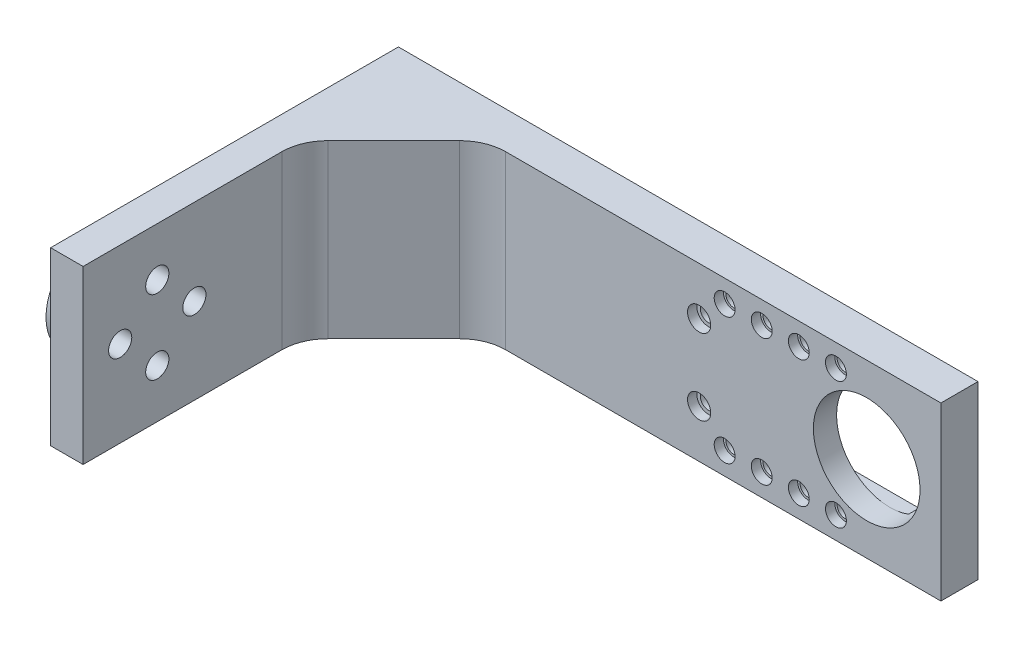
SolidWorks part; units mm, degrees
ref_plane "Front Plane" through (0, 0, 0) normal (0, 0, 1) x (1, 0, 0)
ref_plane "Top Plane" through (0, 0, 0) normal (0, 1, 0) x (1, 0, 0)
ref_plane "Right Plane" through (0, 0, 0) normal (1, 0, 0) x (0, 0, -1)
sketch "Sketch1" plane through (0, 0, 0) normal (0, 1, 0) x (1, 0, 0)
  line L0 (0, 0) -> (0, 75)
  line L1 (0, 75) -> (125, 75)
  line L2 (125, 75) -> (125, 67)
  line L3 (125, 67) -> (7, 67)
  line L4 (7, 67) -> (7, 0)
  line L5 (7, 0) -> (0, 0)
  dimension "D1" = 118
  dimension "D2" = 125
  dimension "D3" = 8
  dimension "D4" = 67
  dimension "D5" = 75
extrude "Boss-Extrude1" add sketch "Sketch1" along normal blind 37
sketch "Sketch2" plane through (0, 0, -75) normal (0, 0, -1) x (-1, 0, 0)
  line L0 (-125, 18.5) -> (-109, 18.5)
  line L1 (-125, 37) -> (-125, 0) construction
  circle A0 centre (-109, 18.5) radius 11.5
  dimension "D2" = 23
  dimension "D1" = 16
extrude "Cut-Extrude1" cut sketch "Sketch2" against normal up to next contours A0 region at (109, 7.3253, -75)
sketch "Sketch3" plane through (0, 0, -75) normal (0, 0, -1) x (-1, 0, 0)
  line L0 (-125, 32.19) -> (-102.36, 32.19)
  line L1 (-125, 37) -> (-125, 0) construction
  line L2 (-102.36, 32.19) -> (-102.36, 37)
  line L3 (-125, 37) -> (0, 37) construction
  line L4 (-125, 18.5) -> (-57.038, 18.5)
  circle A0 centre (-102.36, 32.19) radius 1.75
  circle A1 centre (-94.36, 32.19) radius 1.75
  circle A2 centre (-86.36, 32.19) radius 1.75
  circle A3 centre (-78.36, 32.19) radius 1.75
  circle A4 centre (-78.36, 4.81) radius 1.75
  circle A5 centre (-86.36, 4.81) radius 1.75
  circle A6 centre (-94.36, 4.81) radius 1.75
  circle A7 centre (-102.36, 4.81) radius 1.75
  dimension "D3" = 3.5
  dimension "D1" = 22.64
  dimension "D2" = 4.81
  dimension "D4" = 4
extrude "Cut-Extrude2" cut sketch "Sketch3" against normal up to next contours A5 | A7 | A6 | A4 | A3 | A2 | A1 | A0 region at (86.36, 4.81, -75)
sketch "Sketch4" plane through (0, 0, -75) normal (0, 0, -1) x (-1, 0, 0)
  line L0 (-113, 30) -> (-113, 7)
  line L4 (-113, 30) -> (-75, 30)
  line L5 (-75, 30) -> (-75, 7)
  line L6 (-75, 7) -> (-113, 7)
  dimension "D3" = 23
  dimension "D4" = 38
  dimension "D5" = 38
sketch "Sketch5" plane through (0, 0, 0) normal (-1, 0, 0) x (0, 0, 1)
  circle A1 centre (-16, 10.5) radius 1.75
  circle A2 centre (-24, 18.5) radius 1.75
  circle A3 centre (-16, 26.5) radius 1.75
  circle A4 centre (-8, 18.5) radius 1.75
  point P13 (-16, 18.5)
  dimension "D4" = 3.5
  dimension "D1" = 4
extrude "Cut-Extrude5" cut sketch "Sketch5" against normal up to next
sketch "Sketch6" plane through (0, 0, 0) normal (-1, 0, 0) x (0, 0, 1)
  line L0 (0, 18.5) -> (-16, 18.5)
  line L1 (0, 37) -> (0, 0) construction
  circle A0 centre (-16, 18.5) radius 11
  circle A1 centre (-16, 10.5) radius 1.75 construction
  circle A2 centre (-24, 18.5) radius 1.75 construction
  circle A3 centre (-16, 26.5) radius 1.75 construction
  circle A4 centre (-8, 18.5) radius 1.75 construction
  circle A5 centre (-16, 10.5) radius 1.75
  circle A6 centre (-24, 18.5) radius 1.75
  circle A7 centre (-16, 26.5) radius 1.75
  circle A8 centre (-8, 18.5) radius 1.75
  circle M1 centre (-8, 18.5) radius 1.75
  circle M2 centre (-16, 26.5) radius 1.75
  circle M3 centre (-24, 18.5) radius 1.75
  circle M4 centre (-16, 10.5) radius 1.75
  dimension "D2" = 22
  dimension "D1" = 16
extrude "Boss-Extrude3" add sketch "Sketch6" along normal blind 6 contours A0 M1 M3 M4 M2 region at (0, 18.5, -26.6889)
extrude "Cut-Extrude6" cut sketch "Sketch4" against normal blind 3
sketch "Sketch7" plane through (75, 0, 0) normal (1, 0, 0) x (0, 0, -1)
  line L4 (75, 7) -> (75, 30)
  line L5 (75, 30) -> (72, 30)
  line L6 (72, 30) -> (72, 7)
  line L7 (72, 7) -> (75, 7)
  line L8 (75, 7) -> (75, 30)
  line L9 (75, 30) -> (72, 30)
  line L10 (72, 30) -> (72, 7)
  line L11 (72, 7) -> (75, 7)
  dimension "D1" = 0
sketch "Sketch9" plane through (0, 0, -67) normal (0, 0, 1) x (1, 0, 0)
  circle A1 centre (78.36, 32.19) radius 2.25
  circle A2 centre (86.36, 32.19) radius 2.25
  circle A3 centre (94.36, 32.19) radius 2.25
  circle A4 centre (102.36, 32.19) radius 2.25
  circle A6 centre (78.36, 4.81) radius 2.25
  circle A7 centre (86.36, 4.81) radius 2.25
  circle A8 centre (94.36, 4.81) radius 2.25
  circle A9 centre (102.36, 4.81) radius 2.25
  dimension "D2" = 4.5
  dimension "D3" = 4.5
  dimension "D4" = 4.5
  dimension "D5" = 4.5
  dimension "D7" = 4.5
  dimension "D8" = 4.5
  dimension "D9" = 4.5
  dimension "D10" = 4.5
extrude "Cut-Extrude8" cut sketch "Sketch9" against normal blind 2
sketch "Sketch10" plane through (7, 0, 0) normal (1, 0, 0) x (0, 0, -1)
  circle A0 centre (24, 18.5) radius 2.5
  circle A1 centre (16, 10.5) radius 2.5
  circle A2 centre (8, 18.5) radius 2.5
  circle A3 centre (16, 26.5) radius 2.5
  dimension "D1" = 5
  dimension "D2" = 5
  dimension "D3" = 5
  dimension "D4" = 5
extrude "Cut-Extrude9" cut sketch "Sketch10" against normal blind 5
chamfer "Chamfer1" distance 20 angle 45 1 edges at (7, 18.5, -67)
fillet "Fillet5" radius 10 2 edges at (7, 18.5, -47) (27, 18.5, -67)
sketch "Sketch11" plane through (0, 0, -67) normal (0, 0, 1) x (1, 0, 0)
  line L0 (78.36, 4.81) -> (72.86, 4.81)
  line L1 (72.86, 4.81) -> (72.86, 10.31)
  line L2 (31.1421, 18.5) -> (74.9862, 18.5)
  line L3 (31.1421, 37) -> (31.1421, 0) construction
  circle A0 centre (72.86, 10.31) radius 1.75
  circle A1 centre (72.86, 26.69) radius 1.75
  dimension "D3" = 3.5
  dimension "D1" = 5.5
  dimension "D2" = 5.5
extrude "Cut-Extrude10" cut sketch "Sketch11" against normal up to next contours A0 | A1 region at (74.0624, 9.1076, -67) region at (72.86, 26.69, -67)
sketch "Sketch12" plane through (0, 0, -67) normal (0, 0, 1) x (1, 0, 0)
  circle A0 centre (72.86, 10.31) radius 2.5
  circle A1 centre (72.86, 26.69) radius 2.5
  dimension "D1" = 5
  dimension "D2" = 5
extrude "Cut-Extrude11" cut sketch "Sketch12" against normal blind 2
extrude "Boss-Extrude4" add sketch "Sketch7" along normal blind 0.5
